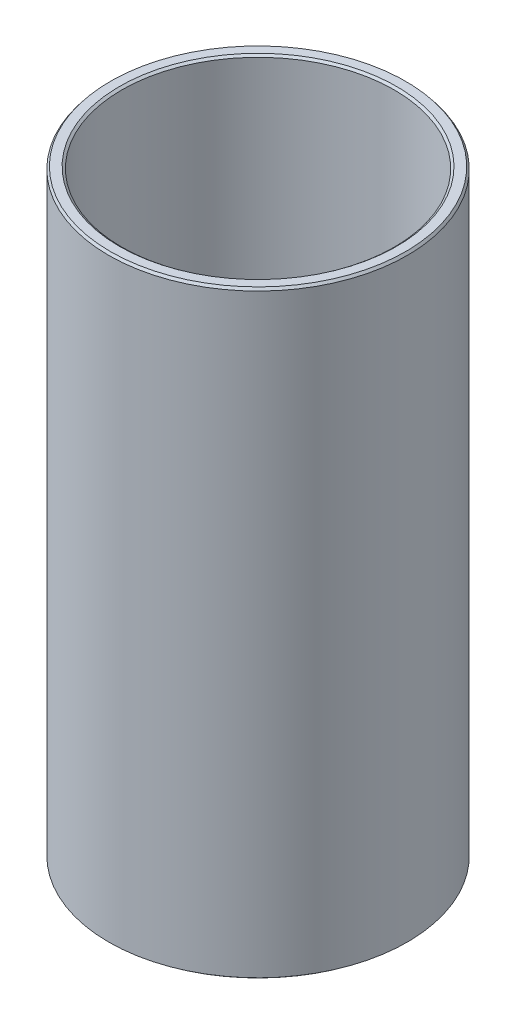
SolidWorks part; units mm, degrees
ref_plane "Front Plane" through (0, 0, 0) normal (0, 0, 1) x (1, 0, 0)
ref_plane "Top Plane" through (0, 0, 0) normal (0, 1, 0) x (1, 0, 0)
ref_plane "Right Plane" through (0, 0, 0) normal (1, 0, 0) x (0, 0, -1)
sketch "Sketch1" plane through (0, 0, 0) normal (0, 1, 0) x (1, 0, 0)
  circle A0 centre (0, 0) radius 57.5
  dimension "SLEEVE_OD" = 115
extrude "Boss-Extrude1" add sketch "Sketch1" along normal blind 230.5296
sketch "Sketch2" plane through (0, 0, 0) normal (0, 1, 0) x (1, 0, 0)
  circle A0 centre (0, 0) radius 52.4445
  dimension "BORE_D" = 104.8891
extrude "Cut-Extrude1" cut sketch "Sketch2" along normal through all
chamfer "Chamfer1" distance 0.8997 angle 37.687 4 edges at (0, 230.5296, 52.4445) (0, 0, 52.4445) (0, 0, 57.5) (0, 230.5296, 57.5) first distance on face at (0, 230.5296, 52.4445) first distance on face at (0, 0, 52.4445) first distance on face at (0, 230.5296, 57.5)
